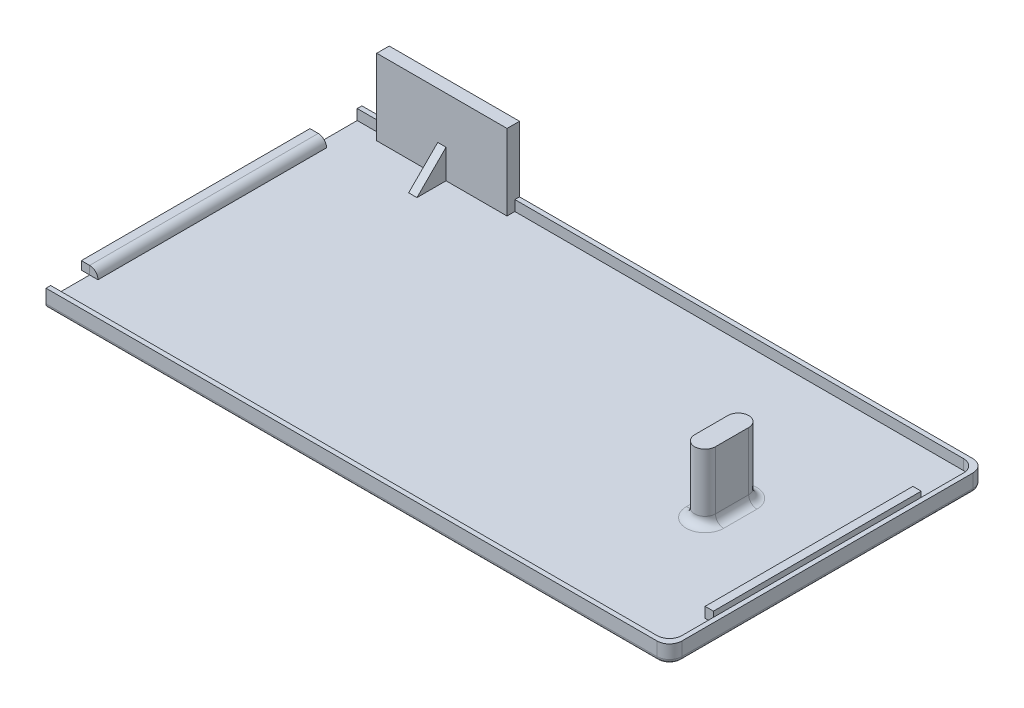
SolidWorks part; units mm, degrees
ref_plane "Front Plane" through (0, 0, 0) normal (0, 0, 1) x (1, 0, 0)
ref_plane "Top Plane" through (0, 0, 0) normal (0, 1, 0) x (1, 0, 0)
ref_plane "Right Plane" through (0, 0, 0) normal (1, 0, 0) x (0, 0, -1)
sketch "Sketch1" plane through (0, 0, 0) normal (0, 1, 0) x (1, 0, 0)
  line L1 (0, 0) -> (147, 0)
  line L2 (0, 0) -> (0, 76)
  line L3 (0, 76) -> (147, 76)
  line L4 (150, 3) -> (150, 73)
  line L5 (0, 0) -> (150, 76) construction
  line L6 (0, 76) -> (150, 0) construction
  arc A0 (150, 3) -> (147, 0) centre (147, 3) cw
  arc A1 (150, 73) -> (147, 76) centre (147, 73) ccw
  point P4 (75, 38)
  dimension "D3" = 3
  dimension "D1" = 150
  dimension "D2" = 76
extrude "Boss-Extrude1" add sketch "Sketch1" along normal blind 4.25 contours L3 A1 L4 A0 L1 L2
sketch "Sketch2" plane through (0, 4.25, 0) normal (0, 1, 0) x (1, 0, 0)
  line L3 (0, 74.875) -> (145.875, 74.875)
  line L7 (0, 0) -> (0, 76) construction
  line L16 (148.875, 71.875) -> (148.875, 4.125)
  line L17 (145.875, 1.125) -> (0, 1.125)
  line L18 (0, 1.125) -> (0, 74.875)
  line L19 (0, 76) -> (147, 76) construction
  line L20 (0, 0) -> (147, 0) construction
  line L21 (150, 3) -> (150, 73) construction
  arc A0 (145.875, 1.125) -> (148.875, 4.125) centre (145.875, 4.125) ccw
  arc A1 (148.875, 71.875) -> (145.875, 74.875) centre (145.875, 71.875) ccw
  dimension "D4" = 3
  dimension "D2" = 1.125
  dimension "D3" = 1.125
  dimension "D1" = 1.125
extrude "Cut-Extrude1" cut sketch "Sketch2" against normal blind 2.5
sketch "Sketch3" plane through (0, 0, 0) normal (0, 1, 0) x (1, 0, 0)
  line L0 (0, 76) -> (147, 76) construction
  line L1 (6.575, 76) -> (37.925, 76)
  line L2 (6.575, 76) -> (6.575, 73)
  line L3 (6.575, 73) -> (37.925, 73)
  line L4 (37.925, 76) -> (37.925, 73)
  line L5 (6.575, 76) -> (37.925, 73) construction
  line L6 (6.575, 73) -> (37.925, 76) construction
  line L7 (0, 74.875) -> (0, 1.125) construction
  point P4 (22.25, 74.5)
  dimension "D1" = 6.575
  dimension "D2" = 3
  dimension "D3" = 31.35
extrude "Boss-Extrude2" add sketch "Sketch3" along normal blind 20
fillet "Fillet1" radius 1 5 edges at (73.5, 0, -76) (150, 0, -38) (73.5, 0, 0) (149.1213, 0, -75.1213) (149.1213, 0, -0.8787)
ref_plane "Plane1" through (0, 0, -38) normal (0, 0, -1) x (-1, 0, 0)
sketch "Sketch4" plane through (0, 0, -38) normal (0, 0, -1) x (-1, 0, 0)
  line L1 (0, 1.75) -> (0, 4.25) construction
  line L2 (0, 3) -> (2, 3)
  line L3 (-37.925, 1.75) -> (-6.575, 1.75) construction
  line L4 (0, 1.75) -> (-145.875, 1.75) construction
  line L5 (-37.925, 1.75) -> (-6.575, 1.75) construction
  arc A0 (-1.25, 1.75) -> (0, 3) centre (0, 1.75) cw
  dimension "D3" = 1.25
  dimension "D4" = 2
sketch "Sketch5" plane through (0, 1.75, 0) normal (0, 1, 0) x (1, 0, 0)
  line L1 (0, 65.5) -> (2, 65.5)
  line L2 (0, 65.5) -> (0, 10.5)
  line L3 (0, 10.5) -> (2, 10.5)
  line L4 (2, 65.5) -> (2, 10.5)
  line L5 (0, 65.5) -> (2, 10.5) construction
  line L6 (0, 10.5) -> (2, 65.5) construction
  line L8 (1.25, 38) -> (0, 38) construction
  line L9 (0, 74.875) -> (0, 1.125) construction
  point P4 (1, 38)
  point P10 (0.625, 38)
  point P11 (0, 38)
  dimension "D1" = 2
  dimension "D2" = 55
sweep "Sweep1" add profiles "Sketch5" path "Sketch4"
sketch "Sketch6" plane through (0, 1.75, 0) normal (0, 1, 0) x (1, 0, 0)
  line L1 (145.575, 63) -> (147.575, 63)
  line L2 (145.575, 63) -> (145.575, 13)
  line L3 (145.575, 13) -> (147.575, 13)
  line L4 (147.575, 63) -> (147.575, 13)
  line L5 (145.575, 63) -> (147.575, 13) construction
  line L6 (145.575, 13) -> (147.575, 63) construction
  line L7 (150, 3) -> (150, 73) construction
  line L8 (148.875, 4.125) -> (148.875, 71.875) construction
  point P4 (146.575, 38)
  point P9 (150, 38)
  point P10 (147.575, 38)
  dimension "D1" = 2
  dimension "D2" = 1.3
  dimension "D3" = 50
extrude "Boss-Extrude3" add sketch "Sketch6" along normal up to surface (2.5 mm away) up to face at (105.1529, 4.25, -38)
ref_plane "Plane2" through (22.25, 0, 0) normal (-1, 0, 0) x (0, 0, 1)
sketch "Sketch7" plane through (22.25, 0, 0) normal (-1, 0, 0) x (0, 0, 1)
  line L0 (-73, 8.75) -> (-66, 1.75)
  line L1 (-73, 20) -> (-73, 1.75) construction
  line L4 (-73, 20) -> (-73, 1.75) construction
  line L5 (-74.875, 1.75) -> (-65.5, 1.75) construction
  dimension "D1" = 7
  dimension "D2" = 7
rib "Rib1" sketch "Sketch7" sketch "Sketch7" thickness 2 extrusion direction parallel to sketch draft on no parameters "D1"=2
sketch "Sketch8" plane through (0, 1.75, 0) normal (0, 1, 0) x (1, 0, 0)
  line L0 (124.5575, 42) -> (124.5575, 34) construction
  line L1 (127.0575, 42) -> (127.0575, 34)
  line L2 (122.0575, 42) -> (122.0575, 34)
  line L3 (150, 3) -> (150, 73) construction
  arc A0 (127.0575, 42) -> (122.0575, 42) centre (124.5575, 42) ccw
  arc A1 (122.0575, 34) -> (127.0575, 34) centre (124.5575, 34) ccw
  point P2 (124.5575, 38)
  point P10 (150, 38)
  point P11 (127.0575, 38)
  dimension "D1" = 5
  dimension "D2" = 8
extrude "Boss-Extrude4" add sketch "Sketch8" along normal blind 16
fillet "Fillet2" radius 2 4 edges at (127.0575, 1.75, -38) (124.5575, 1.75, -44.5) (124.5575, 1.75, -31.5) (122.0575, 1.75, -38)
